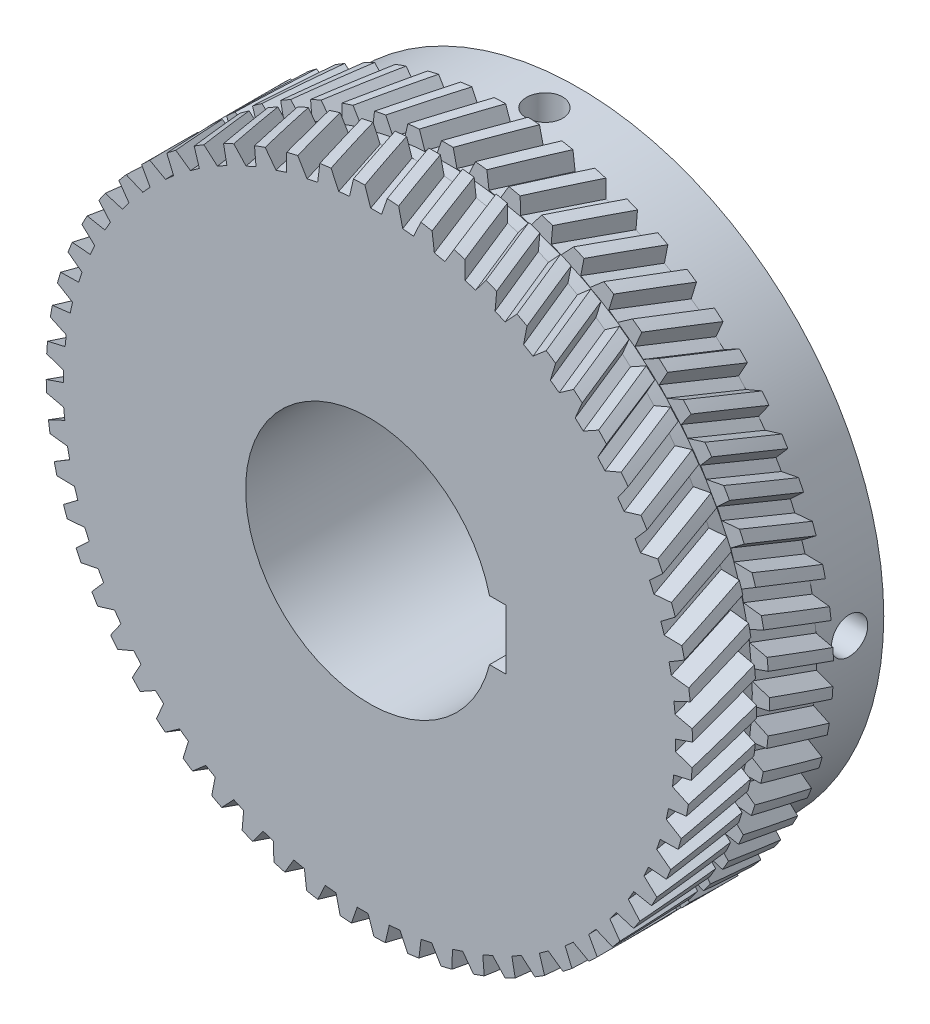
SolidWorks part; units mm, degrees
material "Plain Carbon Steel"
ref_plane "Front Plane" through (0, 0, 0) normal (0, 0, 1) x (1, 0, 0)
ref_plane "Top Plane" through (0, 0, 0) normal (0, 1, 0) x (1, 0, 0)
ref_plane "Right Plane" through (0, 0, 0) normal (1, 0, 0) x (0, 0, -1)
sketch "Sketch1" plane through (0, 0, 0) normal (0, 0, 1) x (1, 0, 0)
  circle A0 centre (0, 0) radius 75.7047
  dimension "D1" = 151.4094
extrude "Boss-Extrude1" add sketch "Sketch1" along normal blind 32.9946
sketch "Sketch2" plane through (0, 0, 0) normal (0, 0, -1) x (-1, 0, 0)
  circle A0 centre (0, 0) radius 71.501
  dimension "D1" = 143.002
extrude "Boss-Extrude2" add sketch "Sketch2" along normal blind 16.002
ref_plane "Plane1" through (75.7047, 0, 0) normal (1, 0, 0) x (0, 0, -1)
sketch "Sketch4" plane through (75.7047, 0, 0) normal (1, 0, 0) x (0, 0, -1)
  line L0 (-16.4946, 6.9104) -> (1.5, 0.5362)
  line L1 (1.5, 0.5362) -> (1.5, -4.7681)
  line L3 (1.5, -4.7681) -> (-16.4946, 1.6061)
  line L4 (-16.4946, 1.6061) -> (-34.4946, -4.7681)
  line L5 (-32.9946, 75.7047) -> (-32.9946, -75.7047) construction
  line L6 (-34.4946, -4.7681) -> (-34.4946, 0.5362)
  line L7 (-34.4946, 0.5362) -> (-16.4946, 6.9104)
  line L8 (0, -75.7047) -> (0, 75.7047) construction
  dimension "D1" = 5
  dimension "D2" = 16.5
  dimension "D3" = 1.5
  dimension "D4" = 1.5
extrude "Cut-Extrude1" cut sketch "Sketch4" against normal blind 4 draft 18
pattern_circular "CirPattern2" count 60 over 360 about axis through (0, 0, 32.9946) along (0, 0, -1) of "Cut-Extrude1"
ref_plane "Plane4" through (0, 0, 16.4973) normal (0, 0, 1) x (1, 0, 0)
sketch "Sketch17" plane through (0, 0, 16.4973) normal (0, 0, 1) x (1, 0, 0)
  circle A0 centre (0, 0) radius 71.7054
  circle A1 centre (0, 0) radius 77.8856
extrude "Cut-Extrude8" cut sketch "Sketch17" against normal blind 1.4986 and the other way blind 1.4986
sketch "Sketch6" plane through (0, 0, -16.002) normal (0, 0, -1) x (-1, 0, 0)
  line L0 (0, 0) -> (-53.3173, 0) construction
  line L1 (-28.1425, 7) -> (-32, 7)
  line L3 (-28.1425, -7) -> (-32, -7)
  line L4 (-32, 7) -> (-32, -7)
  arc A0 (-28.1425, -7) -> (-28.1425, 7) centre (0, 0) ccw
  dimension "D1" = 58
  dimension "D2" = 32
  dimension "D3" = 14
extrude "Cut-Extrude3" cut sketch "Sketch6" against normal through all
sketch "Sketch7" plane through (32, 0, 0) normal (-1, 0, 0) x (0, 0, 1)
  line L0 (-16.002, 7) -> (-16.002, -7) construction
  circle A0 centre (-8.002, 0) radius 4
  dimension "D1" = 8
  dimension "D2" = 8
ref_plane "Plane2" through (0, 20, 0) normal (0, 1, 0) x (1, 0, 0)
sketch "Sketch8" plane through (0, 20, 0) normal (0, 1, 0) x (1, 0, 0)
  line L0 (28.1425, 16.002) -> (-29, 16.002) construction
  circle A0 centre (0, 8.002) radius 4
  dimension "D1" = 8
  dimension "D2" = 8
sketch "Sketch10" plane through (75.7047, 0, 0) normal (1, 0, 0) x (0, 0, -1)
  circle A0 centre (8.002, 0) radius 4.25
  dimension "D1" = 8.5
extrude "Cut-Extrude6" cut sketch "Sketch10" against normal blind 23
ref_plane "Plane3" through (0, 75.7047, 0) normal (0, 1, 0) x (1, 0, 0)
sketch "Sketch11" plane through (0, 75.7047, 0) normal (0, 1, 0) x (1, 0, 0)
  circle A0 centre (0, 8.002) radius 4.25
  dimension "D1" = 8.5
extrude "Cut-Extrude7" cut sketch "Sketch11" against normal blind 28
hole_wizard "M8 Tapped Hole1" positions "Sketch13" profile "Sketch12" tap size "M8" standard "Peddi DIN"
sketch "Sketch13" plane through (52.7047, 0, 0) normal (1, 0, 0) x (0, 0, -1)
  point P0 (8.002, 0)
sketch "Sketch12" plane through (52.7047, 0, -8.002) normal (0, 1, 0) x (0, 0, -1)
  line L0 (0, 0) -> (0, 35.0379)
  line L1 (0, 35.0379) -> (3.4, 32.995)
  line L2 (3.4, 32.995) -> (3.4, 0)
  line L5 (3.4, 0) -> (0, 0)
  line L10 (0, 35.0379) -> (-3.4, 32.995) construction
  line L11 (0, -6.35) -> (0, 107.95) construction
  dimension "Tap Drill Dia." = 6.8
  dimension "Tap Drill Depth" = 32.995
  dimension "Drill Angle" = 118
cosmetic thread "Hole Thread1" parameters "D1"=19.7047, "D2"=8
hole_wizard "M8 Tapped Hole2" positions "Sketch15" profile "Sketch14" tap size "M8" standard "Peddi DIN"
sketch "Sketch15" plane through (0, 47.7047, 0) normal (0, 1, 0) x (1, 0, 0)
  point P0 (0, 8.002)
sketch "Sketch14" plane through (0, 47.7047, -8.002) normal (1, 0, 0) x (0, 0, 1)
  line L0 (0, 0) -> (0, 35.0379)
  line L1 (0, 35.0379) -> (3.4, 32.995)
  line L2 (3.4, 32.995) -> (3.4, 0)
  line L5 (3.4, 0) -> (0, 0)
  line L10 (0, 35.0379) -> (-3.4, 32.995) construction
  line L11 (0, -6.35) -> (0, 107.95) construction
  dimension "Tap Drill Dia." = 6.8
  dimension "Tap Drill Depth" = 32.995
  dimension "Drill Angle" = 118
cosmetic thread "Hole Thread2" parameters "D1"=19.99, "D2"=8
sketch "Sketch19" plane through (0, 0, 32.9946) normal (0, 0, 1) x (1, 0, 0)
  circle A0 centre (0, 0) radius 42.039
  circle A1 centre (0, 0) radius 75.705
  dimension "D1" = 151.41
extrude "Boss-Extrude3" [suppressed] add sketch "Sketch19" along normal blind 25.4
other "Freeze***"
